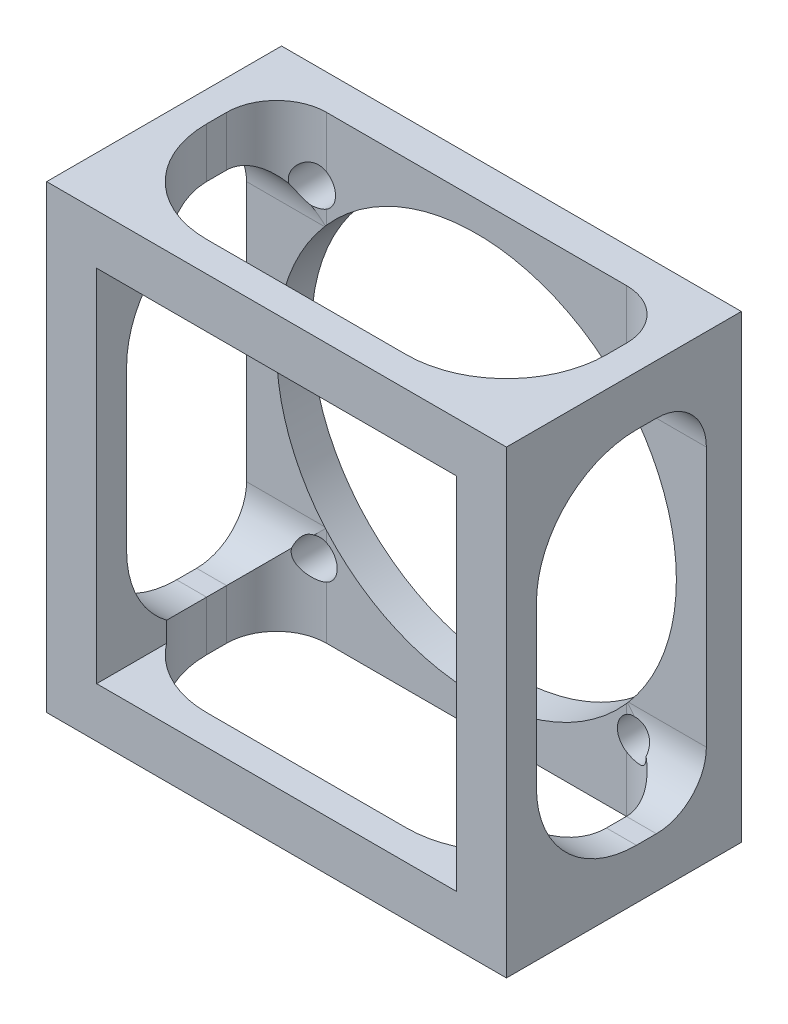
SolidWorks part; units mm, degrees
ref_plane "Front Plane" through (0, 0, 0) normal (0, 0, 1) x (1, 0, 0)
ref_plane "Top Plane" through (0, 0, 0) normal (0, 1, 0) x (1, 0, 0)
ref_plane "Right Plane" through (0, 0, 0) normal (1, 0, 0) x (0, 0, -1)
sketch "Sketch1" plane through (0, 0, 0) normal (0, 0, 1) x (1, 0, 0)
  line L5 (-3.171, 3) -> (42.829, 3)
  line L6 (-3.171, 3) -> (-3.171, -43)
  line L7 (-3.171, -43) -> (42.829, -43)
  line L8 (42.829, 3) -> (42.829, -43)
  circle A0 centre (3.829, -3.7707) radius 1.9
  circle A1 centre (35.829, -4) radius 1.9
  circle A2 centre (35.829, -35.7707) radius 1.9
  circle A3 centre (4, -36) radius 1.9
  circle A4 centre (19.829, -20) radius 20
  point P15 (19.829, -20)
  dimension "D8" = 46
  dimension "D9" = 46
  dimension "D10" = 23
extrude "Boss-Extrude1" add sketch "Sketch1" along normal blind 3.5
ref_plane "Plane1" through (0, 0, 3.5) normal (0, 0, 1) x (1, 0, 0)
sketch "Sketch3" plane through (0, 0, 3.5) normal (0, 0, 1) x (1, 0, 0)
  line L0 (42.829, 3) -> (-3.171, 3) construction
  line L1 (-3.171, -43) -> (42.829, -43)
  line L2 (-3.171, -43) -> (-3.171, 3)
  line L3 (-3.171, 3) -> (42.829, 3)
  line L4 (42.829, -43) -> (42.829, 3)
  dimension "D1" = 46
extrude "Boss-Extrude2" add sketch "Sketch3" along normal blind 20
ref_plane "Plane2" through (0, -43, 0) normal (0, -1, 0) x (-1, 0, 0)
sketch "Sketch4" plane through (0, -43, 0) normal (0, -1, 0) x (-1, 0, 0)
  line L0 (3.171, -23.5) -> (3.171, 0) construction
  line L1 (0.171, -20.5) -> (-39.829, -20.5)
  line L2 (0.171, -20.5) -> (0.171, -3.5)
  line L3 (0.171, -3.5) -> (-39.829, -3.5)
  line L4 (-39.829, -20.5) -> (-39.829, -3.5)
  line L5 (-42.829, -23.5) -> (-42.829, 0) construction
  line L6 (3.171, -23.5) -> (-42.829, -23.5) construction
  line L7 (3.171, 0) -> (-42.829, 0) construction
  dimension "D1" = 3
  dimension "D2" = 3
  dimension "D3" = 3
  dimension "D4" = 3.5
extrude "Cut-Extrude1" cut sketch "Sketch4" against normal through all
ref_plane "Plane3" through (-3.171, 0, 0) normal (-1, 0, 0) x (0, 0, 1)
sketch "Sketch5" plane through (-3.171, 0, 0) normal (-1, 0, 0) x (0, 0, 1)
  line L0 (0, 3) -> (0, -43) construction
  line L1 (3.5, -38) -> (20.5, -38)
  line L2 (3.5, -38) -> (3.5, -2)
  line L3 (3.5, -2) -> (20.5, -2)
  line L4 (20.5, -38) -> (20.5, -2)
  line L5 (23.5, 3) -> (23.5, -43) construction
  line L6 (23.5, 3) -> (0, 3) construction
  line L7 (23.5, -43) -> (0, -43) construction
  dimension "D1" = 3.5
  dimension "D2" = 3
  dimension "D3" = 5
  dimension "D4" = 5
extrude "Cut-Extrude2" cut sketch "Sketch5" against normal through all
ref_plane "Plane4" through (0, 0, 23.5) normal (0, 0, 1) x (1, 0, 0)
sketch "Sketch6" plane through (0, 0, 23.5) normal (0, 0, 1) x (1, 0, 0)
  line L0 (-12.925, -43) -> (12.925, -43) construction
  line L1 (37.829, -38) -> (1.829, -38)
  line L2 (37.829, -38) -> (37.829, -2)
  line L3 (37.829, -2) -> (1.829, -2)
  line L4 (1.829, -38) -> (1.829, -2)
  line L5 (-3.171, 12.925) -> (-3.171, -12.925) construction
  line L6 (42.829, 3) -> (-3.171, 3) construction
  line L7 (42.829, -43) -> (42.829, 3) construction
  dimension "D1" = 5
  dimension "D2" = 5
  dimension "D3" = 5
  dimension "D4" = 5
extrude "Cut-Extrude3" cut sketch "Sketch6" against normal up to next
fillet "Fillet1" radius 10 8 edges at (-1.671, -2, 20.5) (-1.671, -38, 20.5) (41.329, -2, 20.5) (41.329, -38, 20.5) (39.829, -40.5, 20.5) (-0.171, -40.5, 20.5) (-0.171, 0.5, 20.5) (39.829, 0.5, 20.5)
fillet "Fillet2" radius 5 8 edges at (41.329, -2, 3.5) (-0.171, 0.5, 3.5) (-1.671, -38, 3.5) (39.829, -40.5, 3.5) (-0.171, -40.5, 3.5) (41.329, -38, 3.5) (39.829, 0.5, 3.5) (-1.671, -2, 3.5)
